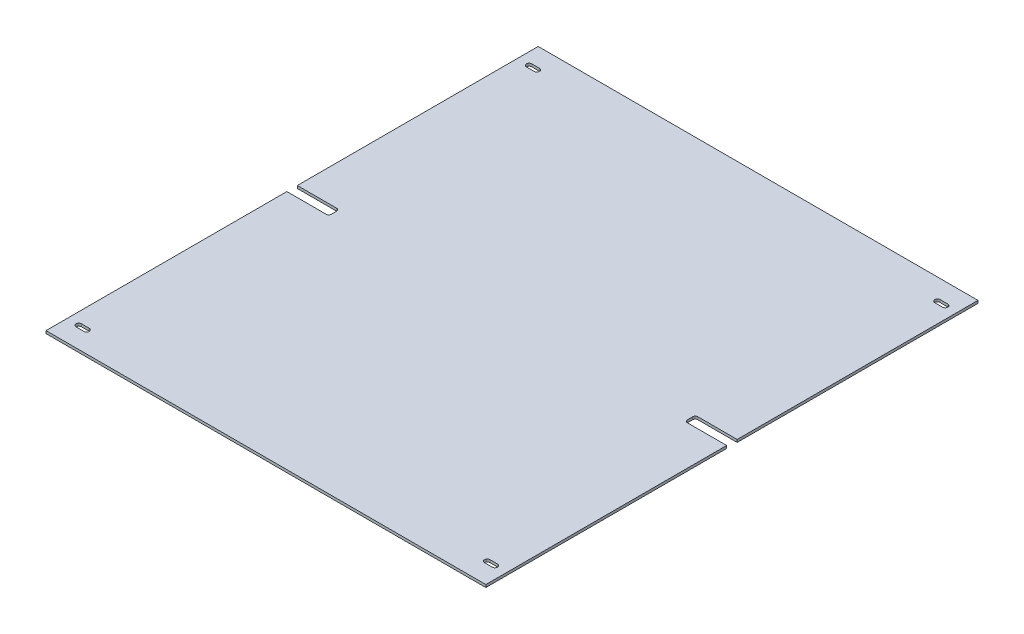
SolidWorks part; units mm, degrees
material "PC High Viscosity"
ref_plane "Front Plane" through (0, 0, 0) normal (0, 0, 1) x (1, 0, 0)
ref_plane "Top Plane" through (0, 0, 0) normal (0, 1, 0) x (1, 0, 0)
ref_plane "Right Plane" through (0, 0, 0) normal (1, 0, 0) x (0, 0, -1)
sketch "Sketch1" plane through (0, 0, 0) normal (0, 1, 0) x (1, 0, 0)
  line L1 (-266.7, -298.45) -> (266.7, -298.45)
  line L2 (-266.7, -298.45) -> (-266.7, 298.45)
  line L3 (-266.7, 298.45) -> (266.7, 298.45)
  line L4 (266.7, -298.45) -> (266.7, 298.45)
  line L5 (-266.7, -298.45) -> (266.7, 298.45) construction
  line L6 (-266.7, 298.45) -> (266.7, -298.45) construction
  point P0 (0, 0)
  dimension "D1" = 596.9
  dimension "D2" = 533.4
extrude "Boss-Extrude1" add sketch "Sketch1" along normal blind 3.175
sketch "Sketch2" plane through (0, 3.175, 0) normal (0, 1, 0) x (1, 0, 0)
  line L0 (-247.65, 298.45) -> (-247.65, -298.45) construction
  line L1 (266.7, 298.45) -> (-266.7, 298.45) construction
  line L2 (-266.7, -298.45) -> (266.7, -298.45) construction
  line L3 (0, 298.45) -> (0, -298.45) construction
  line L5 (247.65, 298.45) -> (247.65, -298.45) construction
  point P10 (-247.65, 273.05)
  point P11 (-247.65, -273.05)
  point P14 (247.65, -273.05)
  point P15 (247.65, 273.05)
  dimension "D1" = 247.65
  dimension "D2" = 25.4
  dimension "D3" = 25.4
hole_wizard "F (0.257) Diameter Slot1" positions "Sketch3" profile "Sketch4" size "F" standard "ANSI Inch" slot yes end condition through all
sketch "Sketch3" plane through (0, 3.175, 0) normal (0, 1, 0) x (1, 0, 0)
  line L0 (-255.5875, 273.05) -> (-239.7125, 273.05) construction
  point P0 (-247.65, 273.05)
  point P5 (-247.65, -273.05)
  point P9 (247.65, 273.05)
  point P12 (247.65, -273.05)
  dimension "D1" = 15.875
sketch "Sketch4" plane through (-247.65, 3.175, -273.05) normal (1, 0, 0) x (0, 0, 1)
  line L0 (0, 0) -> (0, 3.175)
  line L1 (0, 3.175) -> (3.2639, 3.175)
  line L2 (3.2639, 3.175) -> (3.2639, 0)
  line L5 (3.2639, 0) -> (0, 0)
  line L11 (0, -6.35) -> (0, 107.95) construction
  dimension "Thru Hole Dia." = 6.5278
  dimension "Thru Hole Depth" = 3.175
sketch "Sketch5" plane through (0, 3.175, 0) normal (0, 1, 0) x (1, 0, 0)
  line L5 (266.7, -298.45) -> (266.7, 298.45) construction
  line L6 (219.075, 6.35) -> (266.7, 6.35)
  line L7 (215.9, 3.175) -> (215.9, -3.175)
  line L8 (219.075, -6.35) -> (266.7, -6.35)
  line L11 (266.7, 6.35) -> (266.7, -6.35)
  line L12 (215.9, 6.35) -> (266.7, -6.35) construction
  line L17 (215.9, -6.35) -> (266.7, 6.35) construction
  line L18 (0, 298.45) -> (0, -298.45) construction
  line L19 (266.7, 298.45) -> (-266.7, 298.45) construction
  line L20 (-266.7, -298.45) -> (266.7, -298.45) construction
  line L21 (241.3, 0) -> (0, 0) construction
  line L22 (-215.9, -6.35) -> (-266.7, 6.35) construction
  line L23 (-215.9, 6.35) -> (-266.7, -6.35) construction
  line L24 (-266.7, 6.35) -> (-266.7, -6.35)
  line L25 (-219.075, -6.35) -> (-266.7, -6.35)
  line L26 (-215.9, 3.175) -> (-215.9, -3.175)
  line L27 (-219.075, 6.35) -> (-266.7, 6.35)
  arc A0 (219.075, 6.35) -> (215.9, 3.175) centre (219.075, 3.175) ccw
  arc A1 (215.9, -3.175) -> (219.075, -6.35) centre (219.075, -3.175) ccw
  arc A2 (-215.9, -3.175) -> (-219.075, -6.35) centre (-219.075, -3.175) cw
  arc A3 (-219.075, 6.35) -> (-215.9, 3.175) centre (-219.075, 3.175) cw
  point P0 (241.3, 0)
  point P32 (-241.3, 0)
  dimension "D3" = 3.175
  dimension "D1" = 50.8
  dimension "D2" = 12.7
extrude "Cut-Extrude1" cut sketch "Sketch5" against normal through all
